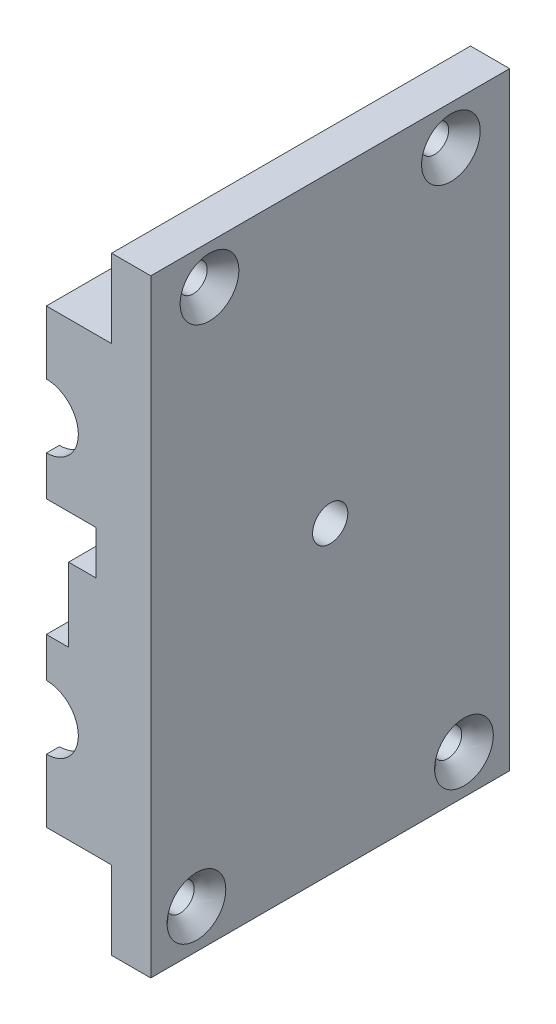
SolidWorks part; units mm, degrees
ref_plane "Front Plane" through (0, 0, 0) normal (0, 0, 1) x (1, 0, 0)
ref_plane "Top Plane" through (0, 0, 0) normal (0, 1, 0) x (1, 0, 0)
ref_plane "Right Plane" through (0, 0, 0) normal (1, 0, 0) x (0, 0, -1)
sketch "Sketch1" plane through (0, 0, 0) normal (0, 0, 1) x (1, 0, 0)
  line L0 (0, 0) -> (0, -93.2)
  line L1 (0, -93.2) -> (-6, -93.2)
  line L2 (-6, -93.2) -> (-6, -81.2)
  line L3 (-6, -81.2) -> (-16, -81.2)
  line L4 (-16, -81.2) -> (-16, -74.2)
  line L5 (-16, -59) -> (-16, -44.3)
  line L6 (-16, -44.3) -> (-8.4, -44.3)
  line L7 (-8.4, -44.3) -> (-8.4, -37.6)
  line L8 (-8.4, -37.6) -> (-16, -37.6)
  line L9 (-16, -37.6) -> (-16, -34.2)
  line L10 (-16, -19) -> (-16, -12)
  line L11 (-16, -12) -> (-6, -12)
  line L12 (-6, -12) -> (-6, 0)
  line L13 (-6, 0) -> (0, 0)
  arc A0 (-16, -74.2) -> (-16, -59) centre (-16, -66.6) ccw
  arc A1 (-16, -34.2) -> (-16, -19) centre (-16, -26.6) ccw
  dimension "D6" = 7.6
  dimension "D7" = 7.6
  dimension "D1" = 6
  dimension "D2" = 12
  dimension "D3" = 12
  dimension "D4" = 14.7
  dimension "D5" = 40
  dimension "D8" = 7
  dimension "D9" = 3.4
  dimension "D11" = 10
  dimension "D12" = 10
extrude "Boss-Extrude1" add sketch "Sketch1" along normal blind 55
ref_plane "Plane1" through (0, 0, 28.5) normal (0, 0, -1) x (-1, 0, 0)
sketch "Sketch2" plane through (0, 0, 28.5) normal (0, 0, -1) x (-1, 0, 0)
  line L0 (16, -34.2) -> (16, -31.5)
  line L1 (16, -21.7) -> (16, -19)
  arc A0 (16, -19) -> (16, -34.2) centre (16, -26.6) ccw
  arc A1 (16, -21.7) -> (16, -31.5) centre (16, -26.6) ccw
  dimension "D1" = 4.9
extrude "Boss-Extrude2" add sketch "Sketch2" along normal blind 2
sketch "Sketch3" plane through (0, 0, 28.5) normal (0, 0, -1) x (-1, 0, 0)
  line L0 (16, -74.2) -> (16, -71.5)
  line L1 (16, -61.7) -> (16, -59)
  arc A0 (16, -59) -> (16, -74.2) centre (16, -66.6) ccw
  arc A1 (16, -61.7) -> (16, -71.5) centre (16, -66.6) ccw
  dimension "D1" = 4.9
extrude "Boss-Extrude3" add sketch "Sketch3" along normal blind 2
ref_plane "Plane2" through (0, 0, 2) normal (0, 0, -1) x (-1, 0, 0)
sketch "Sketch4" plane through (0, 0, 2) normal (0, 0, -1) x (-1, 0, 0)
  line L1 (16, -59) -> (16, -61.7)
  line L2 (16, -74.2) -> (16, -81.2) construction
  line L4 (16, -71.5) -> (16, -74.2)
  line L5 (16, -19) -> (16, -21.7)
  line L6 (16, -31.5) -> (16, -34.2)
  arc A1 (16, -59) -> (16, -74.2) centre (16, -66.6) ccw construction
  arc A2 (16, -74.2) -> (16, -59) centre (16, -66.6) cw
  arc A4 (16, -61.7) -> (16, -71.5) centre (16, -66.6) ccw
  arc A5 (16, -34.2) -> (16, -19) centre (16, -26.6) cw
  arc A6 (16, -21.7) -> (16, -31.5) centre (16, -26.6) ccw
  dimension "D1" = 4.9
  dimension "D2" = 4.9
extrude "Boss-Extrude5" add sketch "Sketch4" along normal blind 2
ref_plane "Plane3" through (0, 0, 53) normal (0, 0, -1) x (-1, 0, 0)
sketch "Sketch5" plane through (0, 0, 53) normal (0, 0, -1) x (-1, 0, 0)
  line L0 (16, -19) -> (16, -21.7)
  line L1 (16, -31.5) -> (16, -34.2)
  line L2 (16, -59) -> (16, -61.7)
  line L3 (16, -71.5) -> (16, -74.2)
  arc A0 (16, -19) -> (16, -34.2) centre (16, -26.6) ccw construction
  arc A1 (16, -34.2) -> (16, -19) centre (16, -26.6) cw
  arc A2 (16, -21.7) -> (16, -31.5) centre (16, -26.6) ccw
  arc A3 (16, -74.2) -> (16, -59) centre (16, -66.6) cw
  arc A4 (16, -61.7) -> (16, -71.5) centre (16, -66.6) ccw
  dimension "D1" = 4.9
extrude "Boss-Extrude6" add sketch "Sketch5" against normal blind 2
sketch "Sketch7" plane through (0, 0, 55) normal (0, 0, 1) x (1, 0, 0)
  line L1 (-16, -44.3) -> (-12.6, -44.3)
  line L2 (-16, -44.3) -> (-16, -55.6)
  line L3 (-16, -55.6) -> (-12.6, -55.6)
  line L4 (-12.6, -44.3) -> (-12.6, -55.6)
  dimension "D1" = 3.4
  dimension "D2" = 11.3
extrude "Cut-Extrude2" cut sketch "Sketch7" against normal up to surface (55 mm away) up to face at (-9.9375, -45.1875, 0)
sketch "Sketch8" plane through (0, 0, 0) normal (1, 0, 0) x (0, 0, -1)
  line L0 (-55, -93.2) -> (-55, 0) construction
  line L1 (0, -93.2) -> (0, 0) construction
  line L2 (-55, 0) -> (0, 0) construction
  line L3 (-55, -93.2) -> (0, -93.2) construction
  circle A0 centre (-46, -6) radius 2.15
  circle A1 centre (-9, -6) radius 2.15
  circle A2 centre (-7, -87.2) radius 2.15
  circle A3 centre (-48, -87.2) radius 2.15
  dimension "D1" = 4.3
  dimension "D2" = 4.3
  dimension "D3" = 4.3
  dimension "D4" = 4.3
  dimension "D5" = 9
  dimension "D6" = 9
  dimension "D7" = 7
  dimension "D8" = 7
  dimension "D9" = 6
  dimension "D10" = 6
  dimension "D11" = 6
  dimension "D12" = 6
extrude "Cut-Extrude3" cut sketch "Sketch8" against normal up to surface (6 mm away) up to face at (-6, -6, 27.5)
sketch "Sketch9" plane through (0, 0, 0) normal (1, 0, 0) x (0, 0, -1)
  line L0 (-55, 0) -> (0, 0) construction
  line L1 (-55, -93.2) -> (-55, 0) construction
  circle A0 centre (-27.5, -46.6) radius 2.7
  dimension "D1" = 5.4
  dimension "D2" = 46.6
  dimension "D3" = 27.5
extrude "Cut-Extrude4" cut sketch "Sketch9" against normal up to surface (12.6 mm away) up to face at (-12.6, -49.95, 27.5)
ref_plane "Plane4" through (-2.5, 0, 0) normal (1, 0, 0) x (0, 0, -1)
sketch "Sketch12" plane through (-2.5, 0, 0) normal (1, 0, 0) x (0, 0, -1)
  circle A0 centre (-46, -6) radius 2.15 construction
  circle A1 centre (-46, -6) radius 2.15
sketch "Sketch13" plane through (0, 0, 0) normal (1, 0, 0) x (0, 0, -1)
  circle A0 centre (-46, -6) radius 4.5
  dimension "D1" = 9
loft "Cut-Loft1" cut profiles "Sketch13", "Sketch12" connector at (0, -8.787, 49.5331) connector at (-2.5, -7.5336, 47.5068)
pattern_linear "LPattern1" count 2 spacing 37 along (0, 0, -1) of "Cut-Loft1"
sketch "Sketch14" plane through (-2.5, 0, 0) normal (1, 0, 0) x (0, 0, -1)
  circle A0 centre (-48, -87.2) radius 2.15 construction
  circle A1 centre (-48, -87.2) radius 2.15
sketch "Sketch15" plane through (0, 0, 0) normal (1, 0, 0) x (0, 0, -1)
  circle A0 centre (-48, -87.2) radius 4.5
  dimension "D1" = 9
loft "Cut-Loft2" cut profiles "Sketch14", "Sketch15" connector at (-2.5, -88.8038, 46.5681) connector at (0, -88.245, 43.623)
pattern_linear "LPattern2" count 2 spacing 41 along (0, 0, -1) of "Cut-Loft2"
